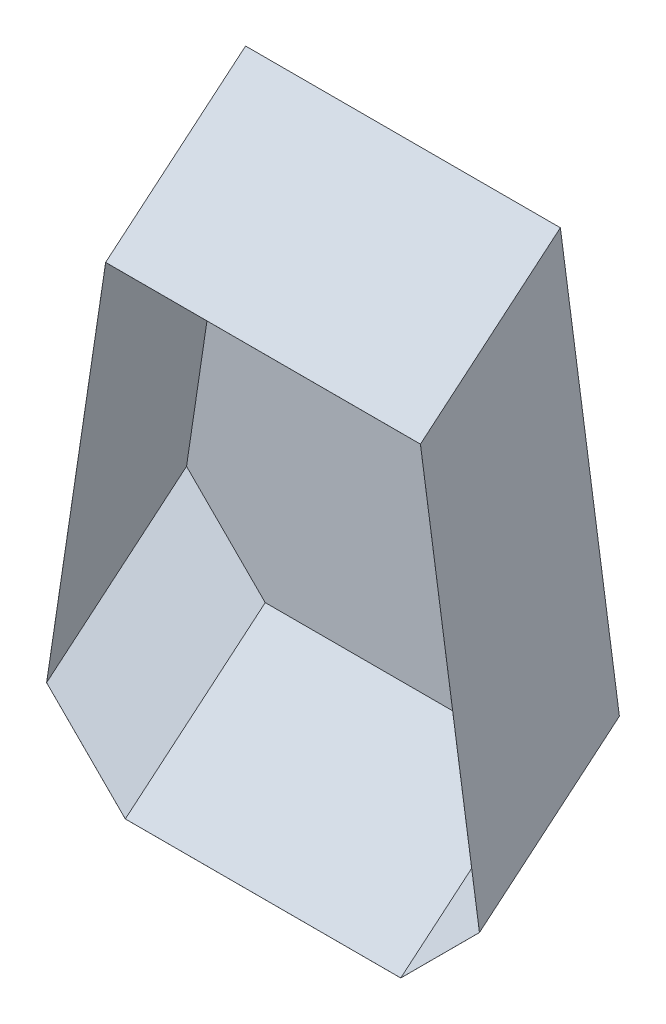
SolidWorks part; units mm, degrees
ref_plane "Plane1" through (0, 0, 0) normal (0, 0, 1) x (1, 0, 0)
ref_plane "Plane2" through (0, 0, 0) normal (0, 1, 0) x (1, 0, 0)
ref_plane "Plane3" through (0, 0, 0) normal (1, 0, 0) x (0, 0, -1)
ref_axis "Axis1" through (-83.9706, 0, 0) along (1, 0, 0)
ref_axis "Axis2" through (0, 0, -25.14) along (0, 0, 1)
ref_axis "Axis3" through (0, 30, 0) along (0, -1, 0)
sketch "Sketch1" plane through (0, 0, 0) normal (0, 0, 1) x (1, 0, 0)
  line L0 (-200, 0) -> (200, 0)
  line L1 (50, 0) -> (-50, 0) construction
  line L2 (200, 0) -> (275, -500)
  line L3 (275, -500) -> (175, -600)
  line L4 (175, -600) -> (-175, -600)
  line L5 (0, -600) -> (0, 0) construction
  line L6 (-275, -500) -> (-175, -600)
  line L7 (-200, 0) -> (-275, -500)
  line L8 (275, -500) -> (0, -500) construction
  dimension "D1" = 400
  dimension "D2" = 100
  dimension "D3" = 500
  dimension "D4" = 100
  dimension "D5" = 350
sketch "Sketch2" plane through (0, 0, 0) normal (1, 0, 0) x (0, 0, -1)
  line L0 (0, 0) -> (-325, 0) construction
  line L1 (-325, 0) -> (-502.8, -149.1919)
  dimension "D1" = 40
  dimension "D2" = 177.8
  dimension "D3" = 325
ref_plane "Plane4" through (0, 0, 325) normal (0, 0, 1) x (1, 0, 0)
sketch "Sketch3" plane through (0, 0, 325) normal (0, 0, 1) x (1, 0, 0)
  line L6 (200, 0) -> (-200, 0)
  line L7 (275, -500) -> (200, 0)
  line L8 (175, -600) -> (275, -500)
  line L9 (-175, -600) -> (175, -600)
  line L10 (-275, -500) -> (-175, -600)
  line L11 (-200, 0) -> (-275, -500)
  line L12 (200, 0) -> (-200, 0)
  line L13 (275, -500) -> (200, 0)
  line L14 (175, -600) -> (275, -500)
  line L15 (-175, -600) -> (175, -600)
  line L16 (-275, -500) -> (-175, -600)
  line L17 (-200, 0) -> (-275, -500)
  dimension "D1" = 0
sweep "Sweep2" add profiles "Sketch3" path "Sketch2"
shell "Shell2" thickness 0.0254 removed face at (0, -515.8586, 502.8)
